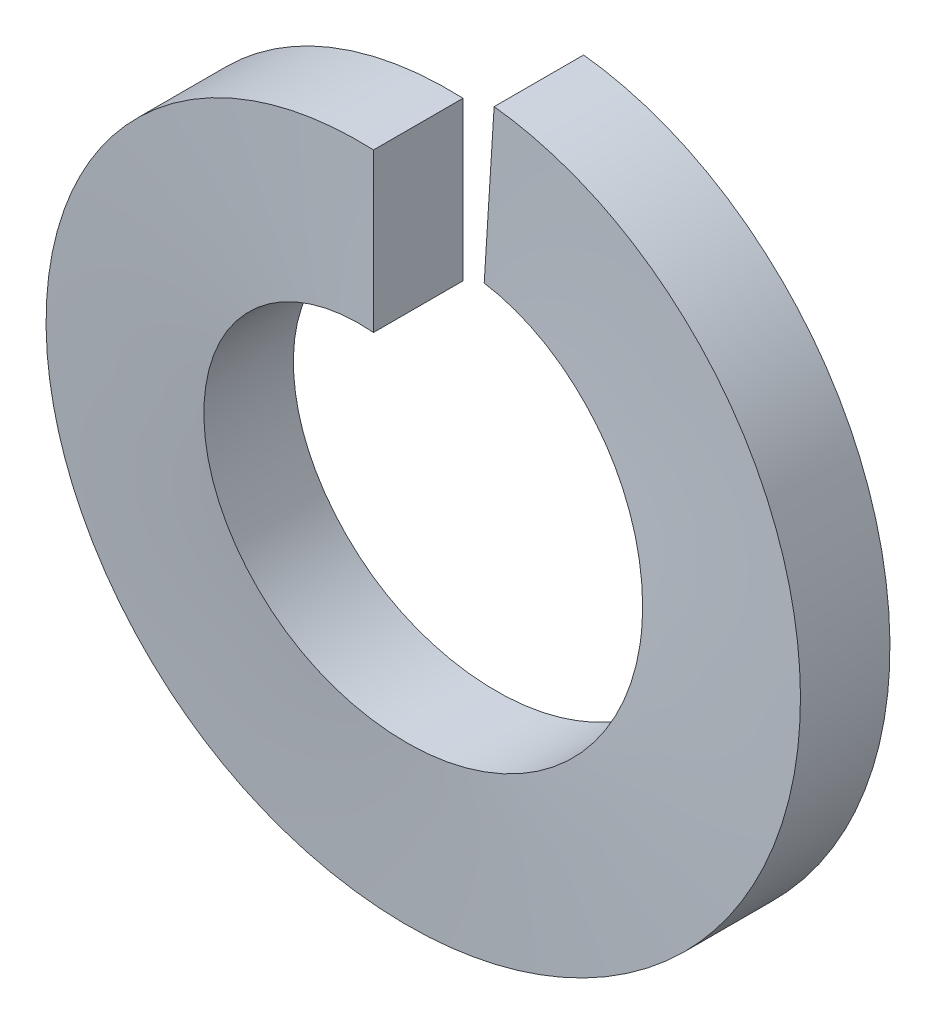
SolidWorks part; units mm, degrees
ref_plane "Front Plane" through (0, 0, 0) normal (0, 0, 1) x (1, 0, 0)
ref_plane "Top Plane" through (0, 0, 0) normal (0, 1, 0) x (1, 0, 0)
ref_plane "Right Plane" through (0, 0, 0) normal (1, 0, 0) x (0, 0, -1)
sketch "Sketch1" plane through (0, 0, 0) normal (0, 0, 1) x (1, 0, 0)
  line L0 (0, 5.9) -> (0, 3.25) construction
  circle A0 centre (0, 0) radius 5.9
  circle A1 centre (0, 0) radius 3.25 construction
  dimension "ID" = 6.5
  dimension "OD" = 11.8
curve "Helix/Spiral1" pitch 1.6667 height 1.65 radius 5.9 left hand yes centre (0, 0, 0) axis (0, 0, -1) start towards (0, 1, 0) parameters "HT"=1.65
sketch "Sketch2" plane through (0, 0, 0) normal (1, 0, 0) x (0, 0, -1)
  line L1 (0, 5.9) -> (-1.5, 5.9)
  line L2 (0, 5.9) -> (0, 3.25)
  line L3 (0, 3.25) -> (-1.5, 3.25)
  line L4 (-1.5, 5.9) -> (-1.5, 3.25)
  dimension "THK" = 1.5
sweep "Sweep1" add profiles "Sketch2" path "Helix/Spiral1"
equation "\"HT@Helix/Spiral1\" = \"THK@Sketch2\"*1.1"
